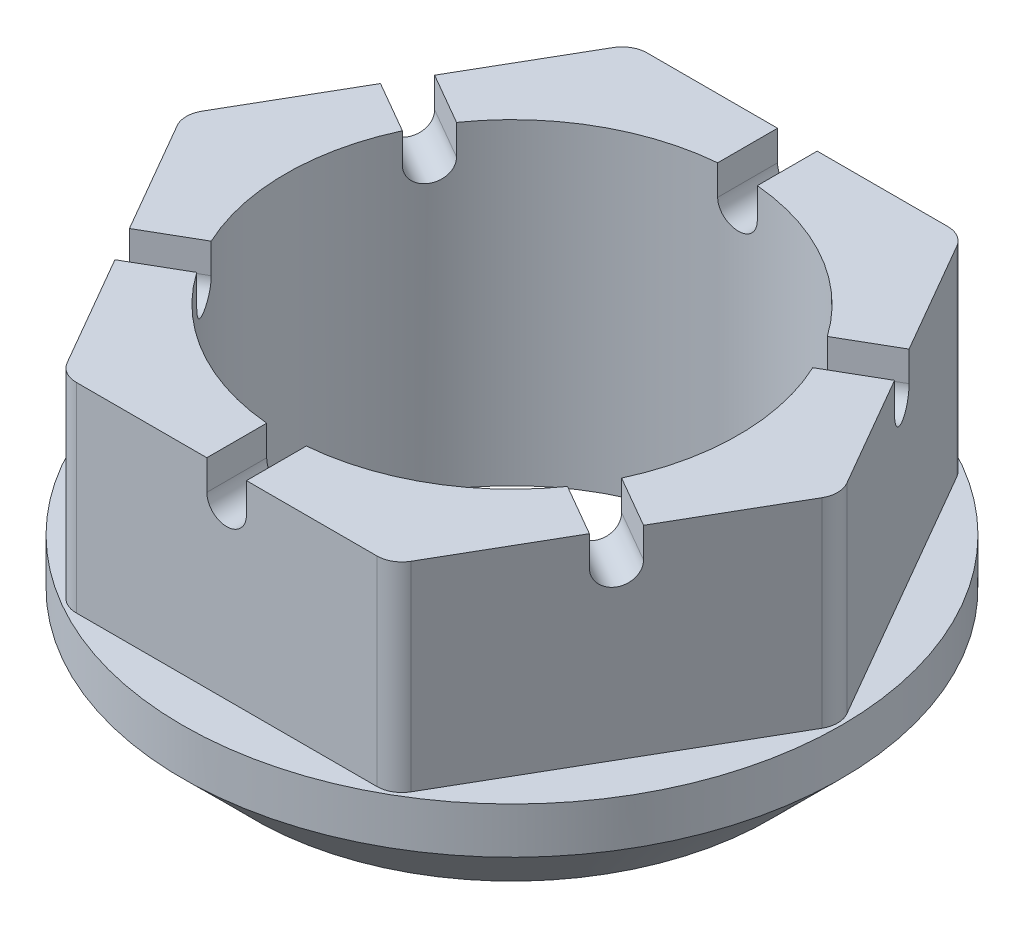
SolidWorks part; units mm, degrees
note: '?' marks a value the reader was unsure of.
material "6061-T6 (SS)"
ref_plane "X-Y Datum" through (0, 0, 0) normal (0, 0, 1) x (1, 0, 0)
ref_plane "X-Z Datum" through (0, 0, 0) normal (0, 1, 0) x (1, 0, 0)
ref_plane "Y-Z Datum" through (0, 0, 0) normal (1, 0, 0) x (0, 0, -1)
sketch "Sketch1" plane through (0, 0, 0) normal (1, 0, 0) x (0, 0, -1)
  line L0 (0, 0) -> (0, 50000) construction
  line L1 (0, 0) -> (-50000, 0) construction
  line L2 (-22.6695, -31.75) -> (-22.6695, 0)
  line L3 (-22.6695, 0) -> (-33, 0)
  line L4 (-33, 0) -> (-33, -24.6194)
  line L6 (-33, -24.6194) -> (-25.8445, -31.75)
  line L7 (-25.8445, -31.75) -> (-22.6695, -31.75)
  dimension "D1" = 66
  dimension "D2" = 3.175
  dimension "D3" = 31.75
  dimension "D4" = 45.339
  dimension "D5" = 45.1
  dimension "D6" = 24.6194
revolve "Revolve1" add sketch "Sketch1" angle 360 about L0
ref_axis "Axis1" through (0, 2.4756, 0) along (0, -1, 0)?
thread "Thread1" [suppressed] pitch 2.1167 start angle 0, offset 0, length 0, pitch 2.1167, diameter 45.339
ref_plane "Plane1" through (22.6695, -31.75, 0) normal (0, 0, 1) x (1, 0, 0)
sketch "Thread Profile1" plane through (22.6695, -31.75, 0) normal (0, 0, 1) x (1, 0, 0)
  line L0 (0, 0) -> (0, 2.1167) construction
  line L1 (0, 0) -> (1.1457, 0.6615)
  line L2 (1.1457, 0.6615) -> (1.1457, 0.926)
  line L3 (1.1457, 0.926) -> (0, 1.5875)
  line L4 (1.1457, 0.7937) -> (0, 0.7937) construction
  line L11 (0, 0) -> (0, 1.5875)
  point P2 (0, 0)
  dimension "Pitch" = 2.1167
  dimension "Profile_Angle" = 60
  dimension "Profile_Land" = 0.2646
  dimension "Profile_Height" = 1.1457
sketch "Sketch4" plane through (0, 0, 0) normal (0, 1, 0) x (1, 0, 0)
  line L1 (16.5, 28.5788) -> (-16.5, 28.5788)
  line L2 (-16.5, 28.5788) -> (-33, 0)
  line L3 (-33, 0) -> (-16.5, -28.5788)
  line L4 (-16.5, -28.5788) -> (16.5, -28.5788)
  line L5 (16.5, -28.5788) -> (33, 0)
  line L6 (33, 0) -> (16.5, 28.5788)
  circle A0 centre (0, 0) radius 28.5788 construction
  circle A1 centre (0, 0) radius 33 construction
  circle A2 centre (0, 0) radius 33 construction
  point P14 (0, 28.5788)
  circle M16 centre (0, 0) radius 33
extrude "Cut-Extrude5" cut sketch "Sketch4" against normal blind 20 contours L6 L5 L4 L3 L2 L1 M16 | L1 M16 | L2 M16 | L3 M16 | L4 M16 | L5 M16
fillet "Fillet4" radius 2.5 6 edges at (16.5, -10, 28.5788) (33, -10, 0) (16.5, -10, -28.5788) (-16.5, -10, -28.5788) (-33, -10, 0) (-16.5, -10, 28.5788)
sketch "Sketch7" plane through (0, 0, 0) normal (0, 0, 1) x (1, 0, 0)
  line L0 (-1.9844, -3) -> (-1.9844, 0)
  line L1 (15.0566, 0) -> (-15.0566, 0) construction
  line L2 (-1.9844, 0) -> (1.9844, 0)
  line L3 (1.9844, 0) -> (1.9844, -3)
  arc A1 (-1.9844, -3) -> (1.9844, -3) centre (0, -3) ccw
  point P7 (0, 0)
  dimension "D1" = 3
  dimension "D2" = 3.9688
extrude "Cut-Extrude6" cut sketch "Sketch7" along normal through all both and the other way through all from surface at -28.5788 starting at face at (0, -10, -28.5788)
pattern_circular "CirPattern2" count 6 over 360 about axis through (0, 0, 0) along (0, 1, 0) of "Cut-Extrude6"
